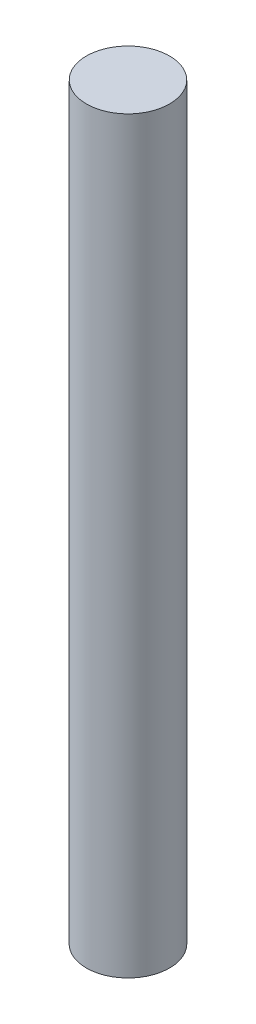
SolidWorks part; units mm, degrees
ref_plane "Front Plane" through (0, 0, 0) normal (0, 0, 1) x (1, 0, 0)
ref_plane "Top Plane" through (0, 0, 0) normal (0, 1, 0) x (1, 0, 0)
ref_plane "Right Plane" through (0, 0, 0) normal (1, 0, 0) x (0, 0, -1)
sketch "Sketch1" plane through (0, 0, 0) normal (0, 1, 0) x (1, 0, 0)
  circle A0 centre (0, 0) radius 2
  dimension "D1" = 4
extrude "Boss-Extrude1" add sketch "Sketch1" along normal blind 36
